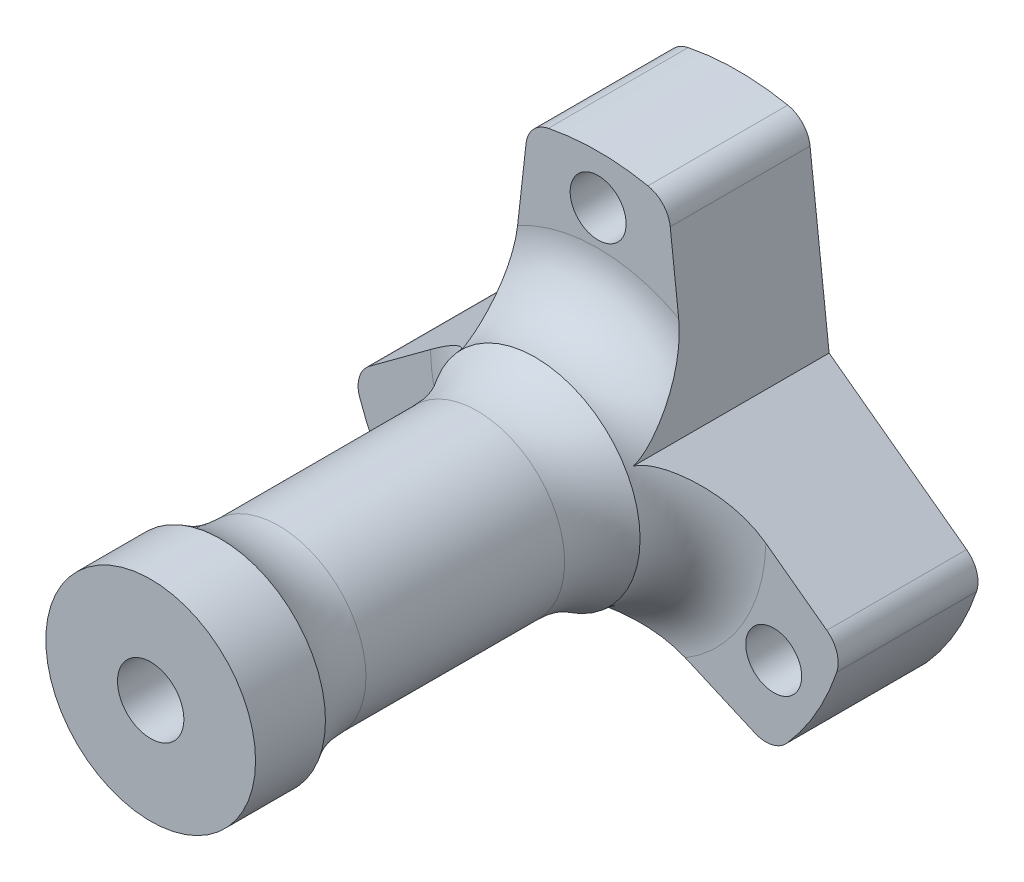
SolidWorks part; units mm, degrees
ref_plane "Front Plane" through (0, 0, 0) normal (0, 0, 1) x (1, 0, 0)
ref_plane "Top Plane" through (0, 0, 0) normal (0, 1, 0) x (1, 0, 0)
ref_plane "Right Plane" through (0, 0, 0) normal (1, 0, 0) x (0, 0, -1)
sketch "Sketch1" plane through (0, 0, 0) normal (0, 0, 1) x (1, 0, 0)
  line L0 (0, 29) -> (0, 0) construction
  line L1 (0, 0) -> (-25.1147, -14.5) construction
  line L2 (0, 0) -> (25.1147, -14.5) construction
  line L3 (10.3111, 31.8128) -> (13.0378, 7.5274)
  line L4 (-10.3111, 31.8128) -> (-13.0378, 7.5274)
  line L5 (-32.7062, -6.9767) -> (-13.0378, 7.5274)
  line L6 (-22.3951, -24.836) -> (0, -15.0548)
  line L7 (22.3951, -24.836) -> (0, -15.0548)
  line L8 (32.7062, -6.9767) -> (13.0378, 7.5274)
  arc A0 (-34.1237, -11.4706) -> (-26.9956, -23.8167) centre (0, 0) ccw
  circle A1 centre (0, 29) radius 4
  circle A2 centre (-25.1147, -14.5) radius 4
  circle A3 centre (25.1147, -14.5) radius 4
  arc A5 (7.128, 35.2873) -> (-7.128, 35.2873) centre (0, 0) ccw
  arc A6 (26.9956, -23.8167) -> (34.1237, -11.4706) centre (0, 0) ccw
  arc A7 (32.7062, -6.9767) -> (34.1237, -11.4706) centre (30.3322, -10.1961) cw
  arc A8 (22.3951, -24.836) -> (26.9956, -23.8167) centre (23.9961, -21.1704) ccw
  arc A9 (-22.3951, -24.836) -> (-26.9956, -23.8167) centre (-23.9961, -21.1704) cw
  arc A10 (-32.7062, -6.9767) -> (-34.1237, -11.4706) centre (-30.3322, -10.1961) ccw
  arc A11 (10.3111, 31.8128) -> (7.128, 35.2873) centre (6.336, 31.3665) ccw
  arc A12 (-10.3111, 31.8128) -> (-7.128, 35.2873) centre (-6.336, 31.3665) cw
  point P23 (34.95, -8.6314)
  point P26 (24.95, -25.9519)
  point P29 (-24.95, -25.9519)
  point P32 (-34.95, -8.6314)
  point P35 (10, 34.5832)
  point P38 (-10, 34.5832)
  dimension "D1" = 72
  dimension "D2" = 8
  dimension "D3" = 8
  dimension "D4" = 8
  dimension "D17" = 4
  dimension "D5" = 120
  dimension "D6" = 120
  dimension "D7" = 29
  dimension "D8" = 29
  dimension "D9" = 29
  dimension "D11" = 10
  dimension "D13" = 10
  dimension "D15" = 10
extrude "Boss-Extrude1" add sketch "Sketch1" along normal blind 20
sketch "Sketch2" plane through (0, 0, 20) normal (0, 0, 1) x (1, 0, 0)
  circle A0 centre (0, 0) radius 15
  dimension "D1" = 30
extrude "Boss-Extrude2" add sketch "Sketch2" along normal blind 9
sketch "Sketch3" plane through (0, 0, 29) normal (0, 0, 1) x (1, 0, 0)
  circle A0 centre (0, 0) radius 12.5
  dimension "D1" = 25
extrude "Boss-Extrude3" add sketch "Sketch3" along normal blind 45
sketch "Sketch5" plane through (0, 0, 74) normal (0, 0, 1) x (1, 0, 0)
  circle A0 centre (0, 0) radius 15 construction
  circle A1 centre (0, 0) radius 15
extrude "Boss-Extrude4" add sketch "Sketch5" along normal blind 10
fillet "Fillet3" radius 9 1 edges at (-15, 0, 20)
fillet "Fillet4" radius 15 2 edges at (12.5, 0, 29) (12.5, 0, 74)
sketch "Sketch6" plane through (0, 0, 84) normal (0, 0, 1) x (1, 0, 0)
  circle A0 centre (0, 0) radius 4.75
  dimension "D1" = 9.5
extrude "Cut-Extrude1" cut sketch "Sketch6" against normal blind 20
